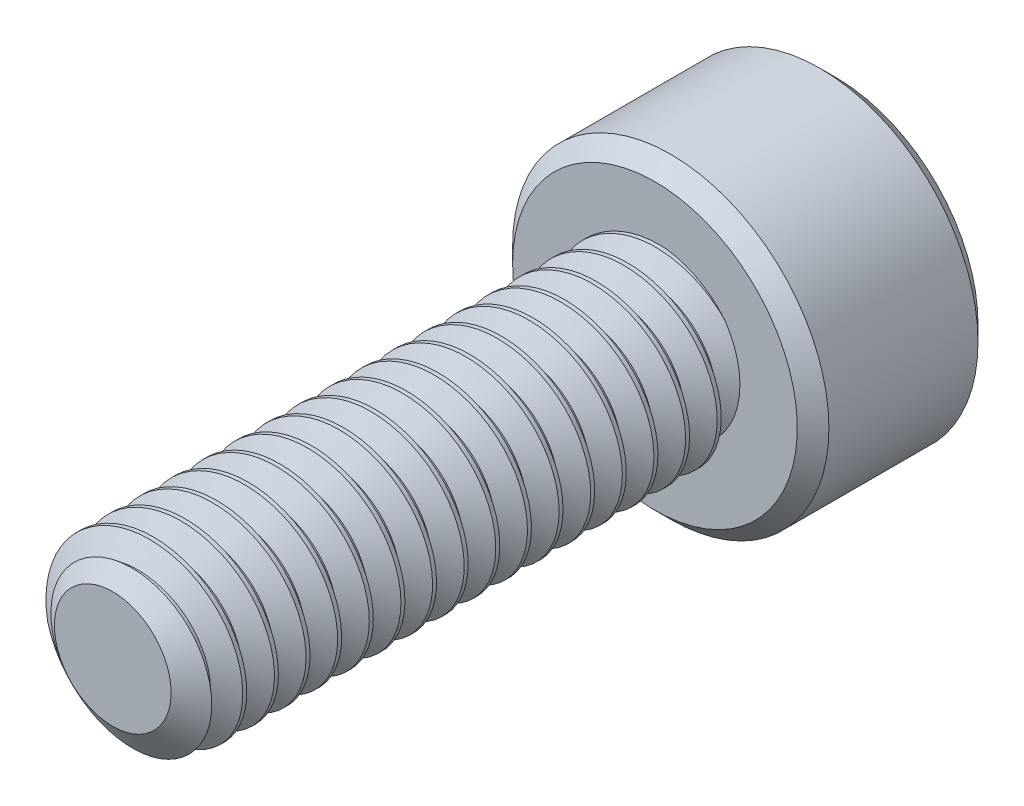
SolidWorks part; units mm, degrees
other "DetailItem1"
ref_plane "Front Plane" through (0, 0, 0) normal (0, 0, 1) x (1, 0, 0)
ref_plane "Top Plane" through (0, 0, 0) normal (0, 1, 0) x (1, 0, 0)
ref_plane "Right Plane" through (0, 0, 0) normal (1, 0, 0) x (0, 0, -1)
sketch "Sketch1" plane through (0, 0, 0) normal (0, 0, 1) x (1, 0, 0)
  circle A0 centre (0, 0) radius 2
  dimension "OD" = 4
extrude "Extrude1" add sketch "Sketch1" against normal blind 12
sketch "Sketch2" plane through (0, 0, 0) normal (0, 0, 1) x (1, 0, 0)
  circle A0 centre (0, 0) radius 2 construction
  circle A1 centre (0, 0) radius 2
curve "Helix/Spiral1" pitch 0.7 height 12.7 radius 2 centre (0, 0, 0) axis (0, 0, -1) start towards (0, 1, 0) parameters "pitch"=0.7
sketch "Sketch3" plane through (0, 0, 0) normal (1, 0, 0) x (0, 0, -1)
  line L0 (-0.6125, 2) -> (-0.35, 1.5453)
  line L1 (-0.35, 1.5453) -> (-0.2625, 1.5453)
  line L2 (-0.2625, 1.5453) -> (0, 2)
  line L3 (-0.6125, 2) -> (0, 2)
  line L4 (-0.3062, 2) -> (-0.3062, 1.5453) construction
  line L5 (-0.4812, 1.7727) -> (-0.1312, 1.7727) construction
  line L6 (0, 2) -> (0, -2) construction
  dimension "D1" = 0.0875
  dimension "D2" = 0.35
  dimension "D3" = 60
sweep "Cut-Sweep1" cut profiles "Sketch3" path "Helix/Spiral1" align with end faces yes
sketch "Sketch4" plane through (0, 0, 0) normal (1, 0, 0) x (0, 0, -1)
  line L0 (0.4962, 2) -> (0, 1.2913)
  line L1 (0, 1.2913) -> (0, 2)
  line L2 (0.4962, 2) -> (0, 2)
  line L3 (-0.6125, 2) -> (0, 2) construction
  line L4 (0, 0) -> (7.0209, 0) construction
  dimension "D1" = 55
  dimension "D2" = 0.254
revolve "Cut-Revolve1" cut sketch "Sketch4" angle 360 about L4
sketch "Sketch6" plane through (0, 0, -12) normal (0, 0, -1) x (-1, 0, 0)
  circle A0 centre (0, 0) radius 3.5
  dimension "head dia" = 7
extrude "Extrude2" add sketch "Sketch6" along normal blind 4
sketch "Sketch7" plane through (0, 0, -16) normal (0, 0, -1) x (-1, 0, 0)
  line L1 (0, 1.7321) -> (-1.5, 0.866)
  line L2 (-1.5, 0.866) -> (-1.5, -0.866)
  line L3 (-1.5, -0.866) -> (0, -1.7321)
  line L4 (0, -1.7321) -> (1.5, -0.866)
  line L5 (1.5, -0.866) -> (1.5, 0.866)
  line L6 (1.5, 0.866) -> (0, 1.7321)
  circle A0 centre (0, 0) radius 1.5 construction
  dimension "hex dia" = 3
extrude "Cut-Extrude1" cut sketch "Sketch7" against normal blind 2.25
sketch "Sketch8" plane through (0, 0, -16) normal (0, 0, -1) x (-1, 0, 0)
  circle A0 centre (0, 0) radius 1.7321
extrude "Cut-Extrude2" cut sketch "Sketch8" against normal through all draft 45
chamfer "Chamfer1" distance 0.35 angle 45 2 edges at (-3.5, 0, -16) (-3.5, 0, -12)
sketch "Sketch10" plane through (0, 0, -12) normal (0, 0, 1) x (1, 0, 0)
  circle A1 centre (0, 0) radius 2
  circle A2 centre (0, 0) radius 2
  dimension "D1" = 0
ref_plane "Plane1" through (0, 0, 0) normal (0, 0, 1) x (1, 0, 0)
extrude "partial thread" [suppressed] add sketch "Sketch10" along normal up to surface (10 mm away) separate body up to plane "Plane1"
chamfer "Chamfer2" [suppressed] distance 0.08 angle 45
combine bodies "Combine1" [suppressed] operation type add bodies to combine 107 108
sketch "Sketch9" plane through (0, 0, 0) normal (1, 0, 0) x (0, 0, -1)
  line L0 (0, 2) -> (0, -2) construction
  line L1 (1.75, 2) -> (1.75, -2) construction
  dimension "D1" = 1.75
equation "\"D3@Helix/Spiral1\" = \"screw length@Extrude1\"+\"pitch@Helix/Spiral1\""
equation "\"D1@Sketch3\" = \"pitch@Helix/Spiral1\"*.125"
equation "\"D2@Sketch3\" = \"pitch@Helix/Spiral1\"*.5"
equation "\"D1@Cut-Extrude1\" = \"hex dia@Sketch7\"*.75"
equation "\"D1@Chamfer1\" = \"head dia@Sketch6\"*.05"
equation "\"D1@Sketch9\" = \"pitch@Helix/Spiral1\"*2.5"
equation "\"D1@Chamfer2\"=\"OD@Sketch1\"*.02"
